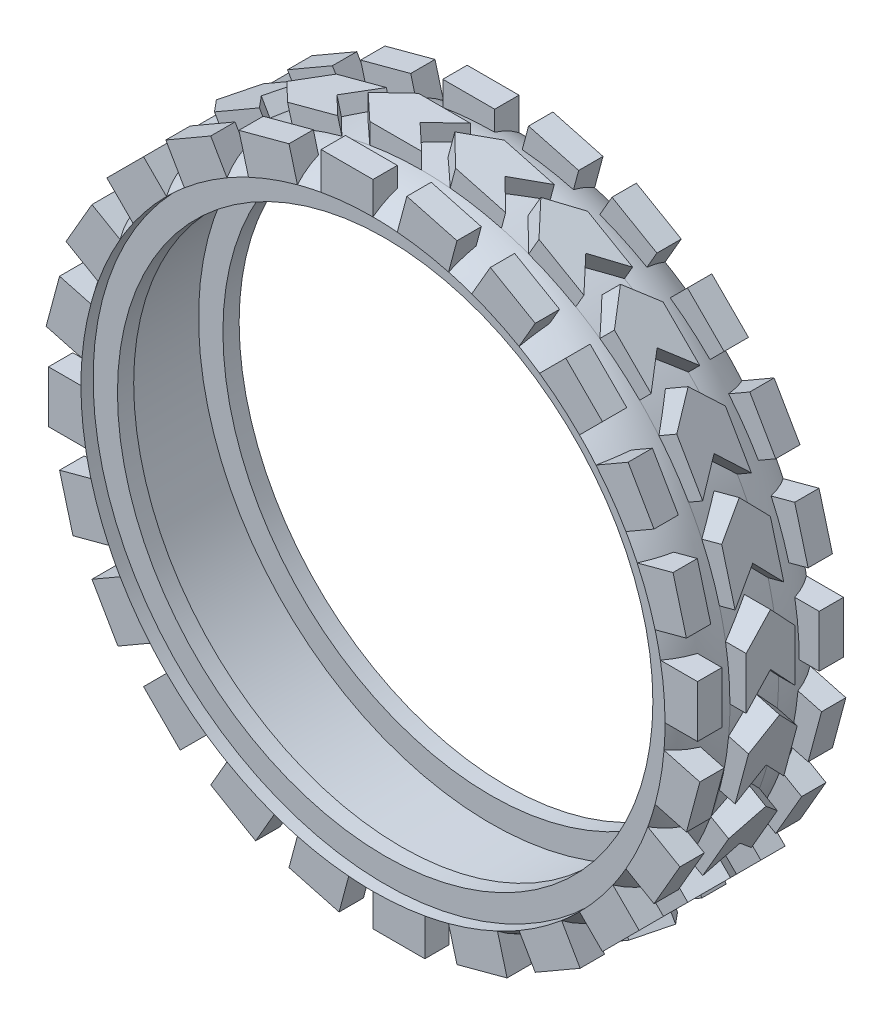
SolidWorks part; units mm, degrees
ref_plane "Front Plane" through (0, 0, 0) normal (0, 0, 1) x (1, 0, 0)
ref_plane "Top Plane" through (0, 0, 0) normal (0, 1, 0) x (1, 0, 0)
ref_plane "Right Plane" through (0, 0, 0) normal (1, 0, 0) x (0, 0, -1)
sketch "Sketch2" plane through (0, 0, 0) normal (1, 0, 0) x (0, 0, -1)
  line L0 (0, 0) -> (0, 38) construction
  line L1 (-9, 38) -> (9, 38)
  line L2 (9, 38) -> (9, 36)
  line L3 (-9, 38) -> (-9, 36)
  line L4 (9, 36) -> (7.5, 36)
  line L5 (-9, 36) -> (-7.5, 36)
  line L6 (7.5, 36) -> (7.5, 33)
  line L7 (-7.5, 36) -> (-7.5, 33)
  line L8 (7.5, 33) -> (5.5, 33)
  line L9 (-11.9819, 0) -> (11.9819, 0)
  line L10 (5.5, 33) -> (5.5, 36)
  line L11 (5.5, 36) -> (0, 36)
  line L12 (0, 36) -> (-5.5, 36)
  line L13 (-5.5, 36) -> (-5.5, 33)
  line L14 (-5.5, 33) -> (-7.5, 33)
  point P11 (0, 31)
  point P15 (0, 0)
  dimension "D1" = 38
  dimension "D2" = 18
  dimension "D3" = 2
  dimension "D4" = 1.5
  dimension "D5" = 3
  dimension "D6" = 2
  dimension "D7" = 2
revolve "Revolve2" add sketch "Sketch2" angle 360 about L9 region at (0, 36.375, 0)
fillet "Fillet1" radius 10 2 edges at (38, 0, 9) (38, 0, -9)
ref_plane "Plane1" through (40, 0, 0) normal (1, 0, 0) x (0, 0, -1)
sketch "Sketch3" plane through (40, 0, 0) normal (1, 0, 0) x (0, 0, -1)
  line L0 (-3, 0) -> (-3, 6.394)
  line L1 (-3, -38) -> (-3, 38) construction
  line L2 (-3, 6.394) -> (0, 9.591)
  line L4 (0, 3.197) -> (-3, 0)
  line L5 (0, 3.197) -> (3, 0)
  line L7 (3, 6.394) -> (0, 9.591)
  line L8 (3, 0) -> (3, 6.394)
  line L9 (-9, 6.394) -> (-6.0009, 6.394)
  line L10 (-9, 36) -> (-9, -36) construction
  line L12 (-6.0009, 6.394) -> (-6.0009, 0)
  line L13 (-6.0009, 0) -> (-9, 0)
  line L14 (-9, 0) -> (-9, 6.394)
  line L15 (0, 55) -> (0, -55) construction
  line L16 (6.0009, 0) -> (9, 0)
  line L17 (6.0009, 6.394) -> (6.0009, 0)
  line L18 (9, 0) -> (9, 6.394)
  line L19 (9, 6.394) -> (6.0009, 6.394)
  point P18 (0, 3.197)
extrude "Boss-Extrude1" add sketch "Sketch3" against normal up to next
pattern_circular "CirPattern1" count 24 over 360 about axis through (0, 0, 0) along (0, 0, 1) of "Boss-Extrude1"
